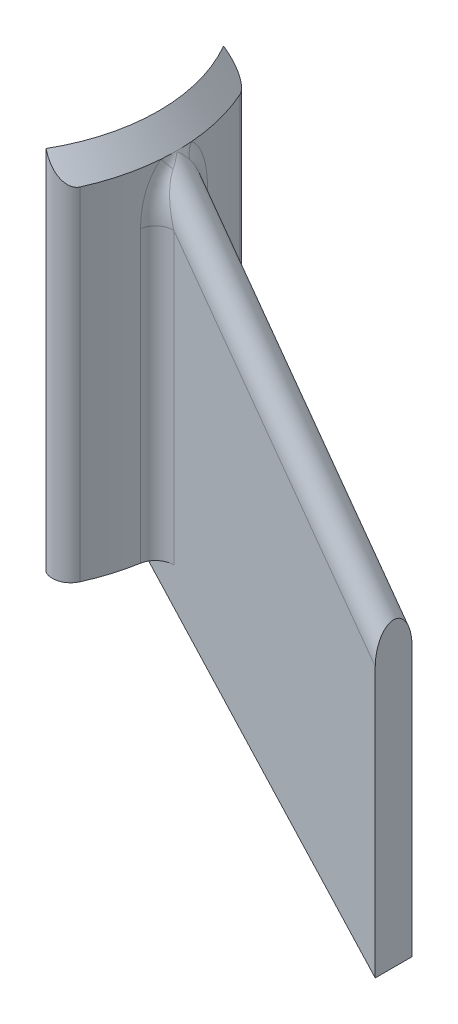
SolidWorks part; units mm, degrees
other "Fin"
ref_plane "Front Plane" through (0, 0, 0) normal (0, 0, 1) x (1, 0, 0)
ref_plane "Top Plane" through (0, 0, 0) normal (0, 1, 0) x (1, 0, 0)
ref_plane "Right Plane" through (0, 0, 0) normal (1, 0, 0) x (0, 0, -1)
sketch "n" plane through (0, 0, 0) normal (0, 0, 1) x (1, 0, 0)
  line L0 (0, 0) -> (0, 31.75)
  line L1 (0, 31.75) -> (20.32, 3.81)
  line L2 (20.32, 3.81) -> (20.32, -22.225)
  line L3 (20.32, -22.225) -> (0, 0)
  dimension "D1" = 20.32
  dimension "D2" = 31.75
  dimension "D3" = 27.94
  dimension "D4" = 53.975
  dimension "D5" = 20.32
extrude "Boss-Extrude1" add sketch "n" along normal blind 1.5875 and the other way blind 1.5875 contours L3 L0 L1 L2
sketch "Sketch1" plane through (0, 0, 0) normal (0, 0, 1) x (1, 0, 0)
  line L0 (0, 0) -> (1.5875, 0)
  line L1 (1.5875, 0) -> (1.5875, 31.75)
  line L2 (1.5875, 31.75) -> (0, 31.75)
  line L3 (0, 31.75) -> (0, 0)
  line L4 (-15.35, -0.6786) -> (-15.35, 49.4231) construction
  dimension "D1" = 1.5875
  dimension "D2" = 15.35
fillet "Fillet1" 2 edges at (10.16, 17.78, 1.5875) (10.16, 17.78, -1.5875) type full round first side face at (10.16, 3.3338, 1.5875) second side face at (10.16, 3.3338, -1.5875) middle face at (10.16, 17.78, 0)
revolve "Revolve1" add sketch "Sketch1" angle 30 about L4 other way angle 30
chamfer "Chamfer1" distance 1.5875 distance2 2.1793 1 edges at (1.5875, 31.75, 0) first distance on face at (-0.2877, 31.75, 0)
fillet "Fillet2" radius 1.5875 5 edges at (1.5129, 13.4853, 1.5875) (1.5871, 24.1766, 0.1138) (-0.6817, 14.7853, 8.4688) (-0.6817, 14.7853, -8.4688) (1.5129, 13.4853, -1.5875)
